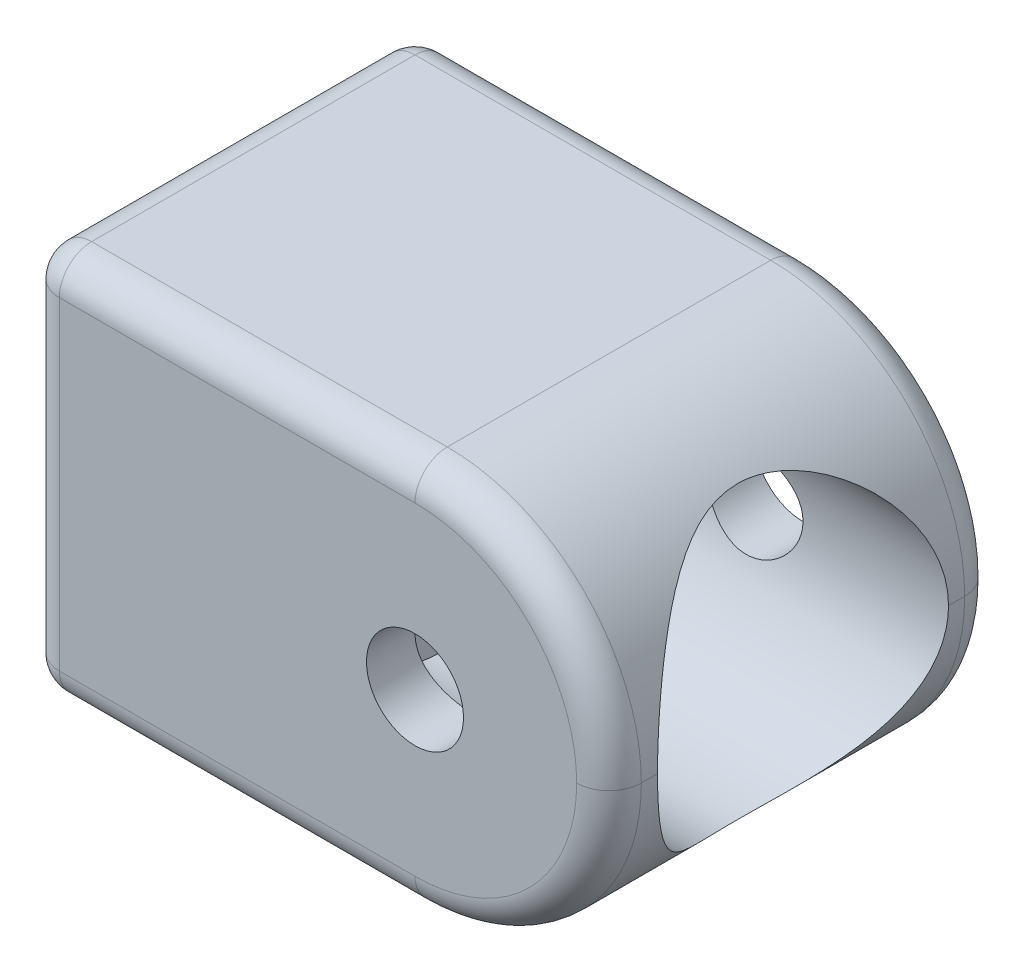
SolidWorks part; units mm, degrees
material "6061 Alloy"
ref_plane "Front Plane" through (0, 0, 0) normal (0, 0, 1) x (1, 0, 0)
ref_plane "Top Plane" through (0, 0, 0) normal (0, 1, 0) x (1, 0, 0)
ref_plane "Right Plane" through (0, 0, 0) normal (1, 0, 0) x (0, 0, -1)
sketch "Sketch1" plane through (0, 0, 0) normal (0, 0, 1) x (1, 0, 0)
  line L1 (12.7, 12.7) -> (-25.4, 12.7)
  line L2 (12.7, 12.7) -> (12.7, -12.7)
  line L3 (12.7, -12.7) -> (-25.4, -12.7)
  line L4 (-25.4, 12.7) -> (-25.4, -12.7)
  circle A0 centre (0, 0) radius 12.7 construction
  circle A1 centre (0, 0) radius 3.175
  dimension "D1" = 25.4
  dimension "D3" = 6.35
  dimension "D2" = 38.1
extrude "Boss-Extrude1" add sketch "Sketch1" along normal blind 25.4
sketch "Sketch3" plane through (0, 0, 25.4) normal (0, 0, 1) x (1, 0, 0)
  line L0 (12.7, 0) -> (-3.175, 0) construction
  line L1 (-3.175, 0) -> (-10.795, 0) construction
  line L2 (12.7, -12.7) -> (12.7, 12.7) construction
  circle A0 centre (0, 0) radius 3.175 construction
  point P10 (12.7, 0)
  dimension "D1" = 7.62
sketch "Sketch2" plane through (12.7, 0, 0) normal (1, 0, 0) x (0, 0, -1)
  line L1 (-25.4, 12.7) -> (0, 12.7) construction
  line L2 (-25.4, 12.7) -> (-25.4, -12.7) construction
  line L3 (-25.4, -12.7) -> (0, -12.7) construction
  line L4 (0, 12.7) -> (0, -12.7) construction
  line L5 (-25.4, 12.7) -> (0, -12.7) construction
  line L6 (-25.4, -12.7) -> (0, 12.7) construction
  circle A0 centre (-12.7, 0) radius 9.525
  circle A1 centre (-12.7, 0) radius 5.5562
  point P4 (-12.7, 0)
  dimension "D1" = 11.1125
  dimension "D2" = 19.05
extrude "Cut-Extrude1" cut sketch "Sketch2" against normal blind 23.495 contours A1 | A0 A1 region at (12.7, 0, 21.9556) region at (12.7, 0, 12.7)
extrude "Cut-Extrude2" cut sketch "Sketch2<4>" against normal through all contours A1 region at (12.7, 0, 12.7)
sketch "Sketch2<4>" plane through (12.7, 0, 0) normal (1, 0, 0) x (0, 0, -1) same geometry as "Sketch2"
fillet "Fillet1" radius 12.7 2 edges at (12.7, -12.7, 12.7) (12.7, 12.7, 12.7)
fillet "Fillet2" radius 2.1167 12 edges at (-12.7, -12.7, 0) (8.9803, -8.9803, 0) (8.9803, 8.9803, 0) (-12.7, -12.7, 25.4) (8.9803, -8.9803, 25.4) (8.9803, 8.9803, 25.4) (-25.4, -12.7, 12.7) (-25.4, 12.7, 12.7) (-25.4, 0, 0) (-25.4, 0, 25.4) (-12.7, 12.7, 0) (-12.7, 12.7, 25.4)
